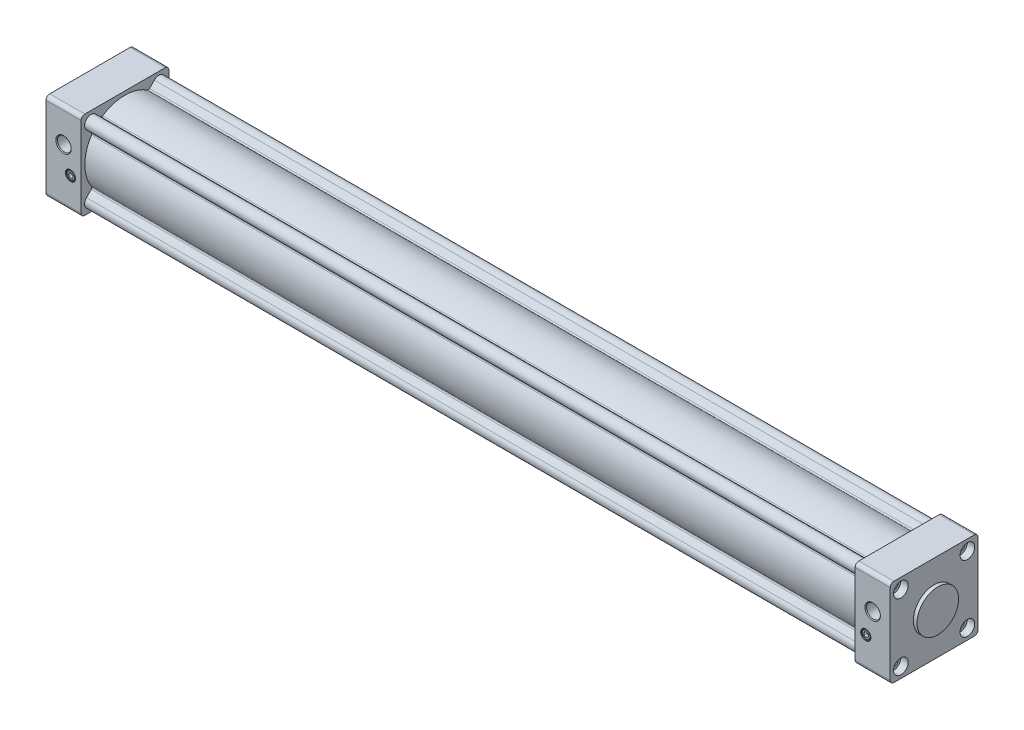
SolidWorks part; units mm, degrees
material "A3钢"
ref_plane "前视基准面" through (0, 0, 0) normal (0, 0, 1) x (1, 0, 0)
ref_plane "上视基准面" through (0, 0, 0) normal (0, 1, 0) x (1, 0, 0)
ref_plane "右视基准面" through (0, 0, 0) normal (1, 0, 0) x (0, 0, -1)
sketch "草图1" plane through (0, 0, 0) normal (1, 0, 0) x (0, 0, -1)
  line L0 (-43.5, -47.5) -> (43.5, -47.5)
  line L1 (47.5, -43.5) -> (47.5, 43.5)
  line L2 (43.5, 47.5) -> (-43.5, 47.5)
  line L3 (-47.5, 43.5) -> (-47.5, -43.5)
  arc A0 (-47.5, -43.5) -> (-43.5, -47.5) centre (-43.5, -43.5) ccw
  arc A1 (43.5, -47.5) -> (47.5, -43.5) centre (43.5, -43.5) ccw
  arc A2 (47.5, 43.5) -> (43.5, 47.5) centre (43.5, 43.5) ccw
  arc A3 (-43.5, 47.5) -> (-47.5, 43.5) centre (-43.5, 43.5) ccw
extrude "凸台-拉伸1" add sketch "草图1" along normal blind 38
sketch "草图2" plane through (0, 0, 0) normal (0, 1, 0) x (1, 0, 0)
  line L0 (-20, 0) -> (-20, 19)
  line L1 (-19, 20) -> (-5, 20)
  line L2 (-5, 20) -> (-5, 21.5)
  line L3 (-4, 22.5) -> (38, 22.5)
  line L4 (38, 22.5) -> (38, 0)
  line L5 (38, 0) -> (-20, 0)
  line L6 (38, 0) -> (-20, 0) construction
  arc A0 (-20, 19) -> (-19, 20) centre (-19, 19) cw
  arc A1 (-5, 21.5) -> (-4, 22.5) centre (-4, 21.5) cw
revolve "旋转1" add sketch "草图2" angle 360 about L6
ref_plane "基准面1" through (38, 0, 0) normal (1, 0, 0) x (0, 0, -1)
sketch "草图3" plane through (38, 0, 0) normal (1, 0, 0) x (0, 0, -1)
  line L0 (-31.7803, -41.6797) -> (-26.5879, -36.4874)
  line L1 (26.5879, -36.4874) -> (31.7803, -41.6797)
  line L2 (41.6797, -31.7803) -> (36.4874, -26.5879)
  line L3 (36.4874, 26.5879) -> (41.6797, 31.7803)
  line L4 (31.7803, 41.6797) -> (26.5879, 36.4874)
  line L5 (-26.5879, 36.4874) -> (-31.7803, 41.6797)
  line L6 (-41.6797, 31.7803) -> (-36.4874, 26.5879)
  line L7 (-36.4874, -26.5879) -> (-41.6797, -31.7803)
  arc A0 (-41.6797, -31.7803) -> (-31.7803, -41.6797) centre (-36.73, -36.73) ccw
  arc A1 (-26.5879, -36.4874) -> (-24.0672, -36.2356) centre (-25.1737, -37.9016) cw
  arc A2 (-24.0672, -36.2356) -> (24.0672, -36.2356) centre (0, 0) ccw
  arc A3 (24.0672, -36.2356) -> (26.5879, -36.4874) centre (25.1737, -37.9016) cw
  arc A4 (31.7803, -41.6797) -> (41.6797, -31.7803) centre (36.73, -36.73) ccw
  arc A5 (36.4874, -26.5879) -> (36.2356, -24.0672) centre (37.9016, -25.1737) cw
  arc A6 (36.2356, -24.0672) -> (36.2356, 24.0672) centre (0, 0) ccw
  arc A7 (36.2356, 24.0672) -> (36.4874, 26.5879) centre (37.9016, 25.1737) cw
  arc A8 (41.6797, 31.7803) -> (31.7803, 41.6797) centre (36.73, 36.73) ccw
  arc A9 (26.5879, 36.4874) -> (24.0672, 36.2356) centre (25.1737, 37.9016) cw
  arc A10 (24.0672, 36.2356) -> (-24.0672, 36.2356) centre (0, 0) ccw
  arc A11 (-24.0672, 36.2356) -> (-26.5879, 36.4874) centre (-25.1737, 37.9016) cw
  arc A12 (-31.7803, 41.6797) -> (-41.6797, 31.7803) centre (-36.73, 36.73) ccw
  arc A13 (-36.4874, 26.5879) -> (-36.2356, 24.0672) centre (-37.9016, 25.1737) cw
  arc A14 (-36.2356, 24.0672) -> (-36.2356, -24.0672) centre (0, 0) ccw
  arc A15 (-36.2356, -24.0672) -> (-36.4874, -26.5879) centre (-37.9016, -25.1737) cw
  circle A16 centre (36, 36) radius 4.35
  circle A17 centre (36, -36) radius 4.35
  circle A18 centre (-36, 36) radius 4.35
  circle A19 centre (-36, -36) radius 4.35
extrude "凸台-拉伸2" add sketch "草图3" along normal blind 838
ref_plane "基准面2" through (914, 0, 0) normal (1, 0, 0) x (0, 0, -1)
sketch "草图4" plane through (914, 0, 0) normal (1, 0, 0) x (0, 0, -1)
  line L0 (-43.5, -47.5) -> (43.5, -47.5)
  line L1 (47.5, -43.5) -> (47.5, 43.5)
  line L2 (43.5, 47.5) -> (-43.5, 47.5)
  line L3 (-47.5, 43.5) -> (-47.5, -43.5)
  arc A0 (-47.5, -43.5) -> (-43.5, -47.5) centre (-43.5, -43.5) ccw
  arc A1 (43.5, -47.5) -> (47.5, -43.5) centre (43.5, -43.5) ccw
  arc A2 (47.5, 43.5) -> (43.5, 47.5) centre (43.5, 43.5) ccw
  arc A3 (-43.5, 47.5) -> (-47.5, 43.5) centre (-43.5, 43.5) ccw
extrude "凸台-拉伸3" add sketch "草图4" against normal blind 38
sketch "草图5" plane through (0, 0, 0) normal (0, 0, 1) x (1, 0, 0)
  line L0 (876, 0) -> (876, 22.5)
  line L1 (876, 22.5) -> (918, 22.5)
  line L2 (918, 22.5) -> (918, 0)
  line L3 (918, 0) -> (876, 0)
  line L4 (918, 0) -> (876, 0) construction
revolve "旋转2" add sketch "草图5" angle 360 about L4 reverse direction yes
ref_plane "基准面3" through (0, 11.5, 0) normal (0, 1, 0) x (1, 0, 0)
sketch "草图6" plane through (0, 11.5, 0) normal (0, 1, 0) x (1, 0, 0)
  line L0 (19, -47.5) -> (10.669, -47.5)
  line L1 (10.669, -47.5) -> (11.525, -46.644)
  line L2 (11.525, -46.644) -> (11.525, -29.5)
  line L3 (11.525, -29.5) -> (19, -25.1843)
  line L4 (19, -25.1843) -> (19, -47.5)
  line L5 (19, -25.1843) -> (19, -47.5) construction
revolve "切除-旋转1" cut sketch "草图6" angle 360 about L5 reverse direction yes
cosmetic thread "装饰螺纹线1" parameters "D1"=16.5, "D2"=16.662
sketch "草图7" plane through (0, 11.5, 0) normal (0, 1, 0) x (1, 0, 0)
  line L0 (895, -47.5) -> (886.669, -47.5)
  line L1 (886.669, -47.5) -> (887.525, -46.644)
  line L2 (887.525, -46.644) -> (887.525, -29.5)
  line L3 (887.525, -29.5) -> (895, -25.1843)
  line L4 (895, -25.1843) -> (895, -47.5)
  line L5 (895, -25.1843) -> (895, -47.5) construction
revolve "切除-旋转2" cut sketch "草图7" angle 360 about L5 reverse direction yes
cosmetic thread "装饰螺纹线2" parameters "D1"=16.5, "D2"=16.662
ref_plane "基准面4" through (0, -11.5, 0) normal (0, 1, 0) x (1, 0, 0)
ref_plane "基准面5" through (0, -14, 0) normal (0, 1, 0) x (1, 0, 0)
sketch "草图8" plane through (0, -14, 0) normal (0, 1, 0) x (1, 0, 0)
  line L0 (26.5, -47.5) -> (20.95, -47.5)
  line L1 (20.95, -47.5) -> (21.45, -47)
  line L2 (21.45, -47) -> (21.45, -44)
  line L3 (21.45, -44) -> (21.95, -44)
  line L4 (21.95, -44) -> (21.95, -46.5)
  line L5 (21.95, -46.5) -> (22.45, -47)
  line L6 (22.45, -47) -> (24, -47)
  line L7 (24, -47) -> (24, -44)
  line L8 (24, -44) -> (26.5, -44)
  line L9 (26.5, -44) -> (26.5, -47.5)
  line L10 (26.5, -44) -> (26.5, -47.5) construction
revolve "切除-旋转3" cut sketch "草图8" angle 360 about L10 reverse direction yes
sketch "草图9" plane through (0, -14, 0) normal (0, 1, 0) x (1, 0, 0)
  line L0 (887.5, -47.5) -> (881.95, -47.5)
  line L1 (881.95, -47.5) -> (882.45, -47)
  line L2 (882.45, -47) -> (882.45, -44)
  line L3 (882.45, -44) -> (882.95, -44)
  line L4 (882.95, -44) -> (882.95, -46.5)
  line L5 (882.95, -46.5) -> (883.45, -47)
  line L6 (883.45, -47) -> (885, -47)
  line L7 (885, -47) -> (885, -44)
  line L8 (885, -44) -> (887.5, -44)
  line L9 (887.5, -44) -> (887.5, -47.5)
  line L10 (887.5, -44) -> (887.5, -47.5) construction
revolve "切除-旋转4" cut sketch "草图9" angle 360 about L10 reverse direction yes
ref_plane "基准面6" through (0, 14, 0) normal (0, 1, 0) x (1, 0, 0)
ref_plane "基准面7" through (0, 0, -36) normal (0, 0, 1) x (1, 0, 0)
sketch "草图10" plane through (0, 0, -36) normal (0, 0, 1) x (1, 0, 0)
  line L0 (20, -36) -> (20, -40.188)
  line L1 (20, -40.188) -> (8.812, -40.188)
  line L2 (8.812, -40.188) -> (8, -41)
  line L3 (8, -41) -> (8, -43.95)
  line L4 (8, -43.95) -> (0, -43.95)
  line L5 (0, -43.95) -> (0, -36)
  line L6 (0, -36) -> (20, -36)
  line L7 (0, -36) -> (20, -36) construction
revolve "切除-旋转5" cut sketch "草图10" angle 360 about L7 reverse direction yes
cosmetic thread "装饰螺纹线3" parameters "D1"=12, "D2"=10
sketch "草图11" plane through (0, 0, 0) normal (1, 0, 0) x (0, 0, -1)
  line L0 (36, -36) -> (36, 36)
  line L1 (36, -36) -> (-36, -36)
pattern_linear "阵列(线性)1" count 2 spacing 72 along (0, 1, 0) count 2 spacing 72 along (0, 0, 1) of "切除-旋转5"
sketch "草图12" plane through (0, 0, -36) normal (0, 0, 1) x (1, 0, 0)
  line L0 (914, -36) -> (914, -43.95)
  line L1 (914, -43.95) -> (906, -43.95)
  line L2 (906, -43.95) -> (906, -41)
  line L3 (906, -41) -> (905.188, -40.188)
  line L4 (905.188, -40.188) -> (894, -40.188)
  line L5 (894, -40.188) -> (894, -36)
  line L6 (894, -36) -> (914, -36)
  line L7 (894, -36) -> (914, -36) construction
revolve "切除-旋转6" cut sketch "草图12" angle 360 about L7 reverse direction yes
cosmetic thread "装饰螺纹线4" parameters "D1"=12, "D2"=10
sketch "草图13" plane through (914, 0, 0) normal (1, 0, 0) x (0, 0, -1)
  line L0 (36, -36) -> (36, 36)
  line L1 (36, -36) -> (-36, -36)
pattern_linear "阵列(线性)2" count 2 spacing 72 along (0, 1, 0) count 2 spacing 72 along (0, 0, 1) of "切除-旋转6"
sketch "草图14" plane through (0, 0, 0) normal (0, 0, 1) x (1, 0, 0)
  line L0 (-20, 0) -> (-20, 12.5)
  line L1 (-20, 12.5) -> (-1.5, 12.5)
  line L2 (-1.5, 12.5) -> (-1.5, 18.2)
  line L3 (-1.5, 18.2) -> (34.5, 18.2)
  line L4 (34.5, 18.2) -> (34.5, 40)
  line L5 (34.5, 40) -> (879.5, 40)
  line L6 (879.5, 40) -> (879.5, 18.2)
  line L7 (879.5, 18.2) -> (915.5, 18.2)
  line L8 (915.5, 18.2) -> (915.5, 0)
  line L9 (915.5, 0) -> (-20, 0)
  line L10 (915.5, 0) -> (-20, 0) construction
revolve "切除-旋转7" cut sketch "草图14" angle 360 about L10 reverse direction yes
ref_plane "基准面8" through (31.5, 0, 0) normal (1, 0, 0) x (0, 0, -1)
ref_plane "基准面9" through (882.5, 0, 0) normal (1, 0, 0) x (0, 0, -1)
ref_plane "基准面10" through (0, 0, 47.5) normal (0, 0, 1) x (1, 0, 0)
ref_plane "基准面11" through (914, 0, 0) normal (1, 0, 0) x (0, 0, -1)
ref_plane "基准面12" through (457, 0, 0) normal (1, 0, 0) x (0, 0, -1)
ref_plane "基准面13" through (39, 0, 0) normal (1, 0, 0) x (0, 0, -1)
ref_plane "基准面14" through (875, 0, 0) normal (1, 0, 0) x (0, 0, -1)
ref_plane "IP_CA_SCREW 1 XY" through (0, 0, 0) normal (-1, 0, 0) x (0, 0, 1)
ref_plane "IP_CA_SCREW 1 XZ" through (0, -36, 0) normal (0, 1, 0) x (1, 0, 0)
ref_plane "IP_CA_SCREW 1 YZ" through (0, 0, 36) normal (0, 0, -1) x (-1, 0, 0)
ref_axis "IP_CA_SCREW 1 X" through (0, -36, 80.9) along (0, 0, -1)
ref_axis "IP_CA_SCREW 1 Y" through (0, 50, 36) along (0, -1, 0)
ref_axis "IP_CA_SCREW 1 Z" through (-80.9, -36, 36) along (1, 0, 0)
sketch3d "IP_CA_SCREW 1"
  point P0 (0, -36, 36)
ref_plane "IP_CA_SCREW 2 XY" through (0, 0, 0) normal (-1, 0, 0) x (0, 0, 1)
ref_plane "IP_CA_SCREW 2 XZ" through (0, -36, 0) normal (0, 1, 0) x (1, 0, 0)
ref_plane "IP_CA_SCREW 2 YZ" through (0, 0, -36) normal (0, 0, -1) x (-1, 0, 0)
ref_axis "IP_CA_SCREW 2 X" through (0, -36, 80.9) along (0, 0, -1)
ref_axis "IP_CA_SCREW 2 Y" through (0, 50, -36) along (0, -1, 0)
ref_axis "IP_CA_SCREW 2 Z" through (-80.9, -36, -36) along (1, 0, 0)
sketch3d "IP_CA_SCREW 2"
  point P0 (0, -36, -36)
ref_plane "IP_CA_SCREW 3 XY" through (0, 0, 0) normal (-1, 0, 0) x (0, 0, 1)
ref_plane "IP_CA_SCREW 3 XZ" through (0, 36, 0) normal (0, 1, 0) x (1, 0, 0)
ref_plane "IP_CA_SCREW 3 YZ" through (0, 0, 36) normal (0, 0, -1) x (-1, 0, 0)
ref_axis "IP_CA_SCREW 3 X" through (0, 36, 80.9) along (0, 0, -1)
ref_axis "IP_CA_SCREW 3 Y" through (0, 50, 36) along (0, -1, 0)
ref_axis "IP_CA_SCREW 3 Z" through (-80.9, 36, 36) along (1, 0, 0)
sketch3d "IP_CA_SCREW 3"
  point P0 (0, 36, 36)
ref_plane "IP_CA_SCREW 4 XY" through (0, 0, 0) normal (-1, 0, 0) x (0, 0, 1)
ref_plane "IP_CA_SCREW 4 XZ" through (0, 36, 0) normal (0, 1, 0) x (1, 0, 0)
ref_plane "IP_CA_SCREW 4 YZ" through (0, 0, -36) normal (0, 0, -1) x (-1, 0, 0)
ref_axis "IP_CA_SCREW 4 X" through (0, 36, 80.9) along (0, 0, -1)
ref_axis "IP_CA_SCREW 4 Y" through (0, 50, -36) along (0, -1, 0)
ref_axis "IP_CA_SCREW 4 Z" through (-80.9, 36, -36) along (1, 0, 0)
sketch3d "IP_CA_SCREW 4"
  point P0 (0, 36, -36)
ref_plane "IP_CA_SCREW_2 1 XY" through (914, 0, 0) normal (1, 0, 0) x (0, 0, -1)
ref_plane "IP_CA_SCREW_2 1 XZ" through (0, -36, 0) normal (0, -1, 0) x (-1, 0, 0)
ref_plane "IP_CA_SCREW_2 1 YZ" through (0, 0, 36) normal (0, 0, -1) x (-1, 0, 0)
ref_axis "IP_CA_SCREW_2 1 X" through (914, -36, 80.9) along (0, 0, -1)
ref_axis "IP_CA_SCREW_2 1 Y" through (914, -50, 36) along (0, 1, 0)
ref_axis "IP_CA_SCREW_2 1 Z" through (80.9, -36, 36) along (-1, 0, 0)
sketch3d "IP_CA_SCREW_2 1"
  point P0 (914, -36, 36)
ref_plane "IP_CA_SCREW_2 2 XY" through (914, 0, 0) normal (1, 0, 0) x (0, 0, -1)
ref_plane "IP_CA_SCREW_2 2 XZ" through (0, -36, 0) normal (0, -1, 0) x (-1, 0, 0)
ref_plane "IP_CA_SCREW_2 2 YZ" through (0, 0, -36) normal (0, 0, -1) x (-1, 0, 0)
ref_axis "IP_CA_SCREW_2 2 X" through (914, -36, 80.9) along (0, 0, -1)
ref_axis "IP_CA_SCREW_2 2 Y" through (914, -50, -36) along (0, 1, 0)
ref_axis "IP_CA_SCREW_2 2 Z" through (80.9, -36, -36) along (-1, 0, 0)
sketch3d "IP_CA_SCREW_2 2"
  point P0 (914, -36, -36)
ref_plane "IP_CA_SCREW_2 3 XY" through (914, 0, 0) normal (1, 0, 0) x (0, 0, -1)
ref_plane "IP_CA_SCREW_2 3 XZ" through (0, 36, 0) normal (0, -1, 0) x (-1, 0, 0)
ref_plane "IP_CA_SCREW_2 3 YZ" through (0, 0, 36) normal (0, 0, -1) x (-1, 0, 0)
ref_axis "IP_CA_SCREW_2 3 X" through (914, 36, 80.9) along (0, 0, -1)
ref_axis "IP_CA_SCREW_2 3 Y" through (914, -50, 36) along (0, 1, 0)
ref_axis "IP_CA_SCREW_2 3 Z" through (80.9, 36, 36) along (-1, 0, 0)
sketch3d "IP_CA_SCREW_2 3"
  point P0 (914, 36, 36)
ref_plane "IP_CA_SCREW_2 4 XY" through (914, 0, 0) normal (1, 0, 0) x (0, 0, -1)
ref_plane "IP_CA_SCREW_2 4 XZ" through (0, 36, 0) normal (0, -1, 0) x (-1, 0, 0)
ref_plane "IP_CA_SCREW_2 4 YZ" through (0, 0, -36) normal (0, 0, -1) x (-1, 0, 0)
ref_axis "IP_CA_SCREW_2 4 X" through (914, 36, 80.9) along (0, 0, -1)
ref_axis "IP_CA_SCREW_2 4 Y" through (914, -50, -36) along (0, 1, 0)
ref_axis "IP_CA_SCREW_2 4 Z" through (80.9, 36, -36) along (-1, 0, 0)
sketch3d "IP_CA_SCREW_2 4"
  point P0 (914, 36, -36)
ref_plane "IP_CH 1 XY" through (0, 0, 47.5) normal (0, 0, 1) x (1, 0, 0)
ref_plane "IP_CH 1 XZ" through (0, -14, 0) normal (0, -1, 0) x (-1, 0, 0)
ref_plane "IP_CH 1 YZ" through (26.5, 0, 0) normal (1, 0, 0) x (0, 0, -1)
ref_axis "IP_CH 1 X" through (-80.9, -14, 47.5) along (1, 0, 0)
ref_axis "IP_CH 1 Y" through (26.5, -50, 47.5) along (0, 1, 0)
ref_axis "IP_CH 1 Z" through (26.5, -14, 80.9) along (0, 0, -1)
sketch3d "IP_CH 1"
  point P0 (26.5, -14, 47.5)
ref_plane "IP_CH 2 XY" through (0, 0, 47.5) normal (0, 0, 1) x (1, 0, 0)
ref_plane "IP_CH 2 XZ" through (0, -14, 0) normal (0, -1, 0) x (-1, 0, 0)
ref_plane "IP_CH 2 YZ" through (887.5, 0, 0) normal (1, 0, 0) x (0, 0, -1)
ref_axis "IP_CH 2 X" through (-80.9, -14, 47.5) along (1, 0, 0)
ref_axis "IP_CH 2 Y" through (887.5, -50, 47.5) along (0, 1, 0)
ref_axis "IP_CH 2 Z" through (887.5, -14, 80.9) along (0, 0, -1)
sketch3d "IP_CH 2"
  point P0 (887.5, -14, 47.5)
ref_plane "IP_DUMMY XY" through (0, 0, 0) normal (-1, 0, 0) x (0, 0, 1)
ref_plane "IP_DUMMY XZ" through (0, 0, 0) normal (0, 1, 0) x (1, 0, 0)
ref_plane "IP_DUMMY YZ" through (0, 0, 0) normal (0, 0, -1) x (-1, 0, 0)
ref_axis "IP_DUMMY X" through (0, 0, 80.9) along (0, 0, -1)
ref_axis "IP_DUMMY Y" through (0, 50, 0) along (0, -1, 0)
ref_axis "IP_DUMMY Z" through (-80.9, 0, 0) along (1, 0, 0)
sketch3d "IP_DUMMY"
  point P0 (0, 0, 0)
ref_plane "IP_LB XY" through (0, 0, 0) normal (-1, 0, 0) x (0, 0, 1)
ref_plane "IP_LB XZ" through (0, 0, 0) normal (0, 1, 0) x (1, 0, 0)
ref_plane "IP_LB YZ" through (0, 0, 0) normal (0, 0, -1) x (-1, 0, 0)
ref_axis "IP_LB X" through (0, 0, 80.9) along (0, 0, -1)
ref_axis "IP_LB Y" through (0, 50, 0) along (0, -1, 0)
ref_axis "IP_LB Z" through (-80.9, 0, 0) along (1, 0, 0)
sketch3d "IP_LB"
  point P0 (0, 0, 0)
ref_plane "IP_LB_2 XY" through (914, 0, 0) normal (1, 0, 0) x (0, 0, -1)
ref_plane "IP_LB_2 XZ" through (0, 0, 0) normal (0, -1, 0) x (-1, 0, 0)
ref_plane "IP_LB_2 YZ" through (0, 0, 0) normal (0, 0, -1) x (-1, 0, 0)
ref_axis "IP_LB_2 X" through (914, 0, 80.9) along (0, 0, -1)
ref_axis "IP_LB_2 Y" through (914, -50, 0) along (0, 1, 0)
ref_axis "IP_LB_2 Z" through (80.9, 0, 0) along (-1, 0, 0)
sketch3d "IP_LB_2"
  point P0 (914, 0, 0)
ref_plane "IP_LB_SCREW 1 XY" through (0, 0, 0) normal (-1, 0, 0) x (0, 0, 1)
ref_plane "IP_LB_SCREW 1 XZ" through (0, -36, 0) normal (0, 1, 0) x (1, 0, 0)
ref_plane "IP_LB_SCREW 1 YZ" through (0, 0, 36) normal (0, 0, -1) x (-1, 0, 0)
ref_axis "IP_LB_SCREW 1 X" through (0, -36, 80.9) along (0, 0, -1)
ref_axis "IP_LB_SCREW 1 Y" through (0, 50, 36) along (0, -1, 0)
ref_axis "IP_LB_SCREW 1 Z" through (-80.9, -36, 36) along (1, 0, 0)
sketch3d "IP_LB_SCREW 1"
  point P0 (0, -36, 36)
ref_plane "IP_LB_SCREW 2 XY" through (0, 0, 0) normal (-1, 0, 0) x (0, 0, 1)
ref_plane "IP_LB_SCREW 2 XZ" through (0, -36, 0) normal (0, 1, 0) x (1, 0, 0)
ref_plane "IP_LB_SCREW 2 YZ" through (0, 0, -36) normal (0, 0, -1) x (-1, 0, 0)
ref_axis "IP_LB_SCREW 2 X" through (0, -36, 80.9) along (0, 0, -1)
ref_axis "IP_LB_SCREW 2 Y" through (0, 50, -36) along (0, -1, 0)
ref_axis "IP_LB_SCREW 2 Z" through (-80.9, -36, -36) along (1, 0, 0)
sketch3d "IP_LB_SCREW 2"
  point P0 (0, -36, -36)
ref_plane "IP_LB_SCREW_2 1 XY" through (914, 0, 0) normal (1, 0, 0) x (0, 0, -1)
ref_plane "IP_LB_SCREW_2 1 XZ" through (0, -36, 0) normal (0, -1, 0) x (-1, 0, 0)
ref_plane "IP_LB_SCREW_2 1 YZ" through (0, 0, 36) normal (0, 0, -1) x (-1, 0, 0)
ref_axis "IP_LB_SCREW_2 1 X" through (914, -36, 80.9) along (0, 0, -1)
ref_axis "IP_LB_SCREW_2 1 Y" through (914, -50, 36) along (0, 1, 0)
ref_axis "IP_LB_SCREW_2 1 Z" through (80.9, -36, 36) along (-1, 0, 0)
sketch3d "IP_LB_SCREW_2 1"
  point P0 (914, -36, 36)
ref_plane "IP_LB_SCREW_2 2 XY" through (914, 0, 0) normal (1, 0, 0) x (0, 0, -1)
ref_plane "IP_LB_SCREW_2 2 XZ" through (0, -36, 0) normal (0, -1, 0) x (-1, 0, 0)
ref_plane "IP_LB_SCREW_2 2 YZ" through (0, 0, -36) normal (0, 0, -1) x (-1, 0, 0)
ref_axis "IP_LB_SCREW_2 2 X" through (914, -36, 80.9) along (0, 0, -1)
ref_axis "IP_LB_SCREW_2 2 Y" through (914, -50, -36) along (0, 1, 0)
ref_axis "IP_LB_SCREW_2 2 Z" through (80.9, -36, -36) along (-1, 0, 0)
sketch3d "IP_LB_SCREW_2 2"
  point P0 (914, -36, -36)
ref_plane "IP_ROD XY" through (0, 0, 0) normal (-1, 0, 0) x (0, 0, 1)
ref_plane "IP_ROD XZ" through (0, 0, 0) normal (0, 1, 0) x (1, 0, 0)
ref_plane "IP_ROD YZ" through (0, 0, 0) normal (0, 0, -1) x (-1, 0, 0)
ref_axis "IP_ROD X" through (0, 0, 80.9) along (0, 0, -1)
ref_axis "IP_ROD Y" through (0, 50, 0) along (0, -1, 0)
ref_axis "IP_ROD Z" through (-80.9, 0, 0) along (1, 0, 0)
sketch3d "IP_ROD"
  point P0 (0, 0, 0)
ref_plane "IP_SCREW 1 XY" through (31.5, 0, 0) normal (-1, 0, 0) x (0, 0, 1)
ref_plane "IP_SCREW 1 XZ" through (0, -36, 0) normal (0, 1, 0) x (1, 0, 0)
ref_plane "IP_SCREW 1 YZ" through (0, 0, 36) normal (0, 0, -1) x (-1, 0, 0)
ref_axis "IP_SCREW 1 X" through (31.5, -36, 80.9) along (0, 0, -1)
ref_axis "IP_SCREW 1 Y" through (31.5, 50, 36) along (0, -1, 0)
ref_axis "IP_SCREW 1 Z" through (-80.9, -36, 36) along (1, 0, 0)
sketch3d "IP_SCREW 1"
  point P0 (31.5, -36, 36)
ref_plane "IP_SCREW 2 XY" through (31.5, 0, 0) normal (-1, 0, 0) x (0, 0, 1)
ref_plane "IP_SCREW 2 XZ" through (0, -36, 0) normal (0, 1, 0) x (1, 0, 0)
ref_plane "IP_SCREW 2 YZ" through (0, 0, -36) normal (0, 0, -1) x (-1, 0, 0)
ref_axis "IP_SCREW 2 X" through (31.5, -36, 80.9) along (0, 0, -1)
ref_axis "IP_SCREW 2 Y" through (31.5, 50, -36) along (0, -1, 0)
ref_axis "IP_SCREW 2 Z" through (-80.9, -36, -36) along (1, 0, 0)
sketch3d "IP_SCREW 2"
  point P0 (31.5, -36, -36)
ref_plane "IP_SCREW 3 XY" through (31.5, 0, 0) normal (-1, 0, 0) x (0, 0, 1)
ref_plane "IP_SCREW 3 XZ" through (0, 36, 0) normal (0, 1, 0) x (1, 0, 0)
ref_plane "IP_SCREW 3 YZ" through (0, 0, 36) normal (0, 0, -1) x (-1, 0, 0)
ref_axis "IP_SCREW 3 X" through (31.5, 36, 80.9) along (0, 0, -1)
ref_axis "IP_SCREW 3 Y" through (31.5, 50, 36) along (0, -1, 0)
ref_axis "IP_SCREW 3 Z" through (-80.9, 36, 36) along (1, 0, 0)
sketch3d "IP_SCREW 3"
  point P0 (31.5, 36, 36)
ref_plane "IP_SCREW 4 XY" through (31.5, 0, 0) normal (-1, 0, 0) x (0, 0, 1)
ref_plane "IP_SCREW 4 XZ" through (0, 36, 0) normal (0, 1, 0) x (1, 0, 0)
ref_plane "IP_SCREW 4 YZ" through (0, 0, -36) normal (0, 0, -1) x (-1, 0, 0)
ref_axis "IP_SCREW 4 X" through (31.5, 36, 80.9) along (0, 0, -1)
ref_axis "IP_SCREW 4 Y" through (31.5, 50, -36) along (0, -1, 0)
ref_axis "IP_SCREW 4 Z" through (-80.9, 36, -36) along (1, 0, 0)
sketch3d "IP_SCREW 4"
  point P0 (31.5, 36, -36)
ref_plane "IP_SCREW_2 1 XY" through (882.5, 0, 0) normal (1, 0, 0) x (0, 0, -1)
ref_plane "IP_SCREW_2 1 XZ" through (0, -36, 0) normal (0, -1, 0) x (-1, 0, 0)
ref_plane "IP_SCREW_2 1 YZ" through (0, 0, 36) normal (0, 0, -1) x (-1, 0, 0)
ref_axis "IP_SCREW_2 1 X" through (882.5, -36, 80.9) along (0, 0, -1)
ref_axis "IP_SCREW_2 1 Y" through (882.5, -50, 36) along (0, 1, 0)
ref_axis "IP_SCREW_2 1 Z" through (80.9, -36, 36) along (-1, 0, 0)
sketch3d "IP_SCREW_2 1"
  point P0 (882.5, -36, 36)
ref_plane "IP_SCREW_2 2 XY" through (882.5, 0, 0) normal (1, 0, 0) x (0, 0, -1)
ref_plane "IP_SCREW_2 2 XZ" through (0, -36, 0) normal (0, -1, 0) x (-1, 0, 0)
ref_plane "IP_SCREW_2 2 YZ" through (0, 0, -36) normal (0, 0, -1) x (-1, 0, 0)
ref_axis "IP_SCREW_2 2 X" through (882.5, -36, 80.9) along (0, 0, -1)
ref_axis "IP_SCREW_2 2 Y" through (882.5, -50, -36) along (0, 1, 0)
ref_axis "IP_SCREW_2 2 Z" through (80.9, -36, -36) along (-1, 0, 0)
sketch3d "IP_SCREW_2 2"
  point P0 (882.5, -36, -36)
ref_plane "IP_SCREW_2 3 XY" through (882.5, 0, 0) normal (1, 0, 0) x (0, 0, -1)
ref_plane "IP_SCREW_2 3 XZ" through (0, 36, 0) normal (0, -1, 0) x (-1, 0, 0)
ref_plane "IP_SCREW_2 3 YZ" through (0, 0, 36) normal (0, 0, -1) x (-1, 0, 0)
ref_axis "IP_SCREW_2 3 X" through (882.5, 36, 80.9) along (0, 0, -1)
ref_axis "IP_SCREW_2 3 Y" through (882.5, -50, 36) along (0, 1, 0)
ref_axis "IP_SCREW_2 3 Z" through (80.9, 36, 36) along (-1, 0, 0)
sketch3d "IP_SCREW_2 3"
  point P0 (882.5, 36, 36)
ref_plane "IP_SCREW_2 4 XY" through (882.5, 0, 0) normal (1, 0, 0) x (0, 0, -1)
ref_plane "IP_SCREW_2 4 XZ" through (0, 36, 0) normal (0, -1, 0) x (-1, 0, 0)
ref_plane "IP_SCREW_2 4 YZ" through (0, 0, -36) normal (0, 0, -1) x (-1, 0, 0)
ref_axis "IP_SCREW_2 4 X" through (882.5, 36, 80.9) along (0, 0, -1)
ref_axis "IP_SCREW_2 4 Y" through (882.5, -50, -36) along (0, 1, 0)
ref_axis "IP_SCREW_2 4 Z" through (80.9, 36, -36) along (-1, 0, 0)
sketch3d "IP_SCREW_2 4"
  point P0 (882.5, 36, -36)
ref_plane "IP_SWITCH1 XY" through (39, 0, 0) normal (-1, 0, 0) x (0, 0, 1)
ref_plane "IP_SWITCH1 XZ" through (0, -36.73, 0) normal (0, 1, 0) x (1, 0, 0)
ref_plane "IP_SWITCH1 YZ" through (0, 0, 36.73) normal (0, 0, -1) x (-1, 0, 0)
ref_axis "IP_SWITCH1 X" through (39, -36.73, 80.9) along (0, 0, -1)
ref_axis "IP_SWITCH1 Y" through (39, 50, 36.73) along (0, -1, 0)
ref_axis "IP_SWITCH1 Z" through (-80.9, -36.73, 36.73) along (1, 0, 0)
sketch3d "IP_SWITCH1"
  point P0 (39, -36.73, 36.73)
ref_plane "IP_SWITCH2 XY" through (875, 0, 0) normal (1, 0, 0) x (0, 0, -1)
ref_plane "IP_SWITCH2 XZ" through (0, 36.73, 0) normal (0, -1, 0) x (-1, 0, 0)
ref_plane "IP_SWITCH2 YZ" through (0, 0, 36.73) normal (0, 0, -1) x (-1, 0, 0)
ref_axis "IP_SWITCH2 X" through (875, 36.73, 80.9) along (0, 0, -1)
ref_axis "IP_SWITCH2 Y" through (875, -50, 36.73) along (0, 1, 0)
ref_axis "IP_SWITCH2 Z" through (80.9, 36.73, 36.73) along (-1, 0, 0)
sketch3d "IP_SWITCH2"
  point P0 (875, 36.73, 36.73)
ref_plane "IP_TC XY" through (457, 0, 0) normal (1, 0, 0) x (0, 0, -1)
ref_plane "IP_TC XZ" through (0, 0, 0) normal (0, -1, 0) x (-1, 0, 0)
ref_plane "IP_TC YZ" through (0, 0, 0) normal (0, 0, -1) x (-1, 0, 0)
ref_axis "IP_TC X" through (457, 0, 80.9) along (0, 0, -1)
ref_axis "IP_TC Y" through (457, -50, 0) along (0, 1, 0)
ref_axis "IP_TC Z" through (80.9, 0, 0) along (-1, 0, 0)
sketch3d "IP_TC"
  point P0 (457, 0, 0)
